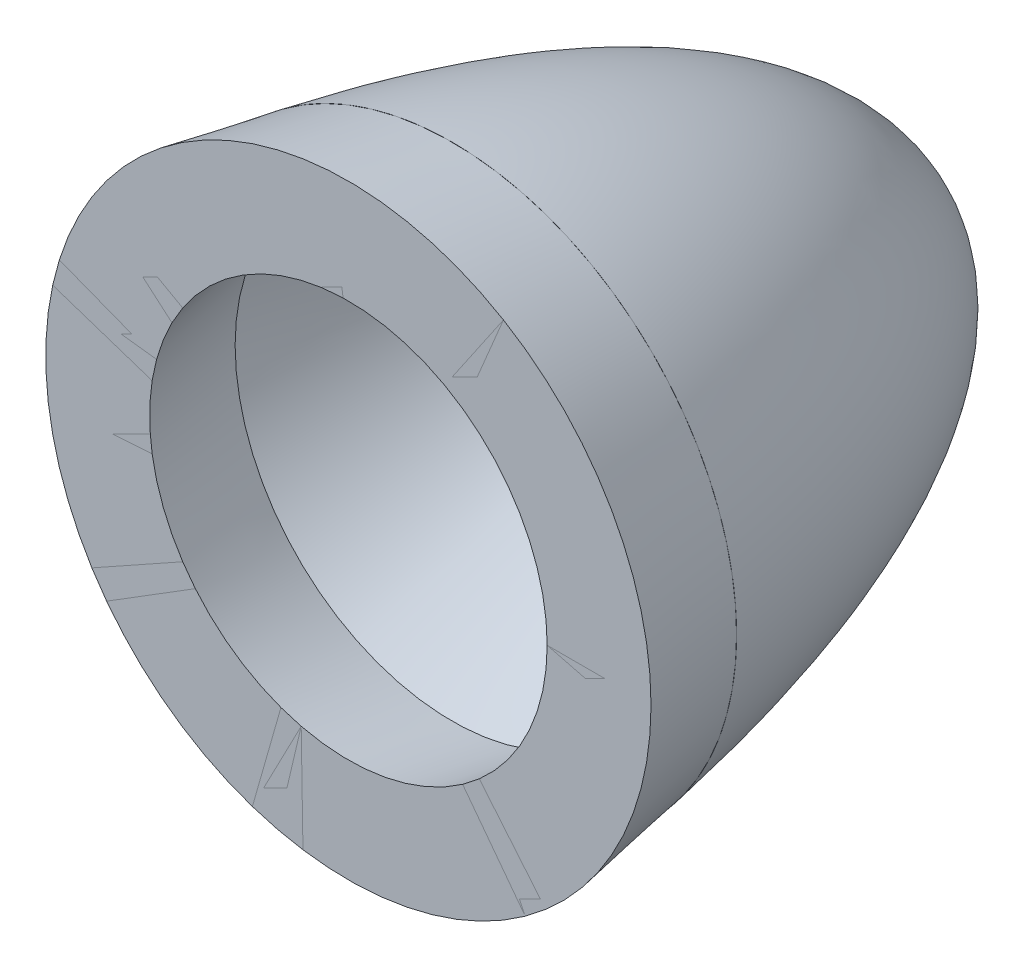
SolidWorks part; units mm, degrees
note: The reader was unsure of these and kept them because the rebuilt part matched: shared geometry of "Эскиз1<3>".
ref_plane "Спереди" through (0, 0, 0) normal (0, 0, 1) x (1, 0, 0)
ref_plane "Сверху" through (0, 0, 0) normal (0, 1, 0) x (1, 0, 0)
ref_plane "Справа" through (0, 0, 0) normal (1, 0, 0) x (0, 0, -1)
sketch "Эскиз1" plane through (0, 0, 0) normal (0, 0, 1) x (1, 0, 0)
  circle A0 centre (0, 0) radius 29.1429
  circle A1 centre (0, 0) radius 19.1429
  dimension "D1" = 10
surface "Поверхность-Заполнить1" sketch "Эскиз1"
extrude "Бобышка-Вытянуть1" add sketch "Эскиз1<3>" against normal blind 10 draft 10
sketch "Эскиз1<3>" plane through (0, 0, 0) normal (0, 0, 1) x (1, 0, 0) same geometry as "Эскиз1"
surface "Поверхность-Заполнить2"
